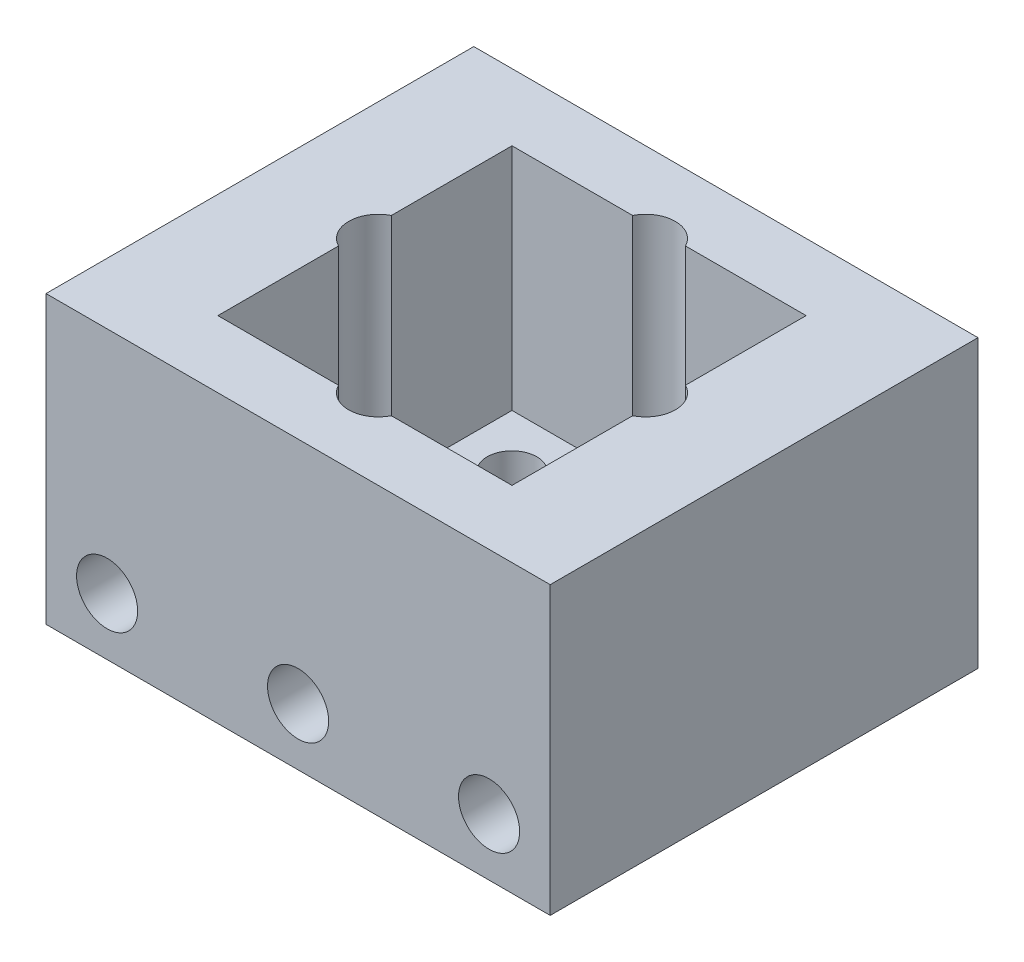
SolidWorks part; units mm, degrees
note: The reader was unsure of these and kept them because the rebuilt part matched: shared geometry of "草图1<4>", "草图1<5>".
ref_plane "前视基准面" through (0, 0, 0) normal (0, 0, 1) x (1, 0, 0)
ref_plane "上视基准面" through (0, 0, 0) normal (0, 1, 0) x (1, 0, 0)
ref_plane "右视基准面" through (0, 0, 0) normal (1, 0, 0) x (0, 0, -1)
sketch "草图1" plane through (0, 0, 0) normal (0, 1, 0) x (1, 0, 0)
  line L0 (0, 0) -> (0, 7.7) construction
  line L1 (0, 0) -> (0, -7.7) construction
  line L2 (0, 0) -> (7.7, 0) construction
  line L3 (0, 0) -> (-7.7, 0) construction
  line L4 (0, 7.7) -> (7.7, 7.7)
  line L5 (7.7, 7.7) -> (7.7, 0)
  line L6 (7.7, -7.7) -> (0, -7.7)
  line L7 (-7.7, -7.7) -> (-7.7, 0)
  line L8 (-7.7, 7.7) -> (0, 7.7)
  line L9 (-7.7, 0) -> (-7.7, 7.7)
  line L10 (-7.7, -7.7) -> (0, -7.7)
  line L11 (7.7, -7.7) -> (7.7, 0)
  line L12 (-7.7, -7.7) -> (-7.7, -11.2)
  line L13 (7.7, -7.7) -> (7.7, -11.2)
  line L14 (-7.7, 11.2) -> (-7.7, 7.7)
  line L15 (7.7, 7.7) -> (7.7, 11.2)
  line L19 (-7.7, 11.2) -> (7.7, 11.2)
  line L22 (7.7, -11.2) -> (-7.7, -11.2)
  line L28 (-7.7, -7.7) -> (-4.7, -7.7)
  line L30 (7.7, 11.2) -> (13.2, 11.2)
  line L32 (13.2, 11.2) -> (13.2, -11.2)
  line L33 (7.7, -11.2) -> (13.2, -11.2)
  line L34 (-7.7, -11.2) -> (-13.2, -11.2)
  line L35 (-13.2, -11.2) -> (-13.2, 11.2)
  line L36 (-13.2, 11.2) -> (-7.7, 11.2)
extrude "凸台-拉伸2" add sketch "草图1" along normal blind 3
extrude "凸台-拉伸3" add sketch "草图1<4>" along normal blind 10 separate body
sketch "草图1<4>" plane through (0, 0, 0) normal (0, 1, 0) x (1, 0, 0) same geometry as "草图1"
extrude "凸台-拉伸4" add sketch "草图1<5>" along normal blind 15
sketch "草图1<5>" plane through (0, 0, 0) normal (0, 1, 0) x (1, 0, 0) same geometry as "草图1"
sketch "草图3" plane through (0, 0, -19.6) normal (0, 0, -1) x (-1, 0, 0)
  line L3 (0, 3) -> (10, 3)
  line L6 (0, 0) -> (0, 3) construction
  line L9 (17.5, 0) -> (-17.5, 0) construction
  line L10 (0, 3) -> (0, 3)
  line L11 (0, 3) -> (-10, 3)
  circle A0 centre (0, 3) radius 1.6
  circle A1 centre (-10, 3) radius 1.6
  circle A2 centre (10, 3) radius 1.6
  point P1 (0, 0)
  point P2 (0, 0)
  point P3 (0, 0)
  point P4 (0, 0)
  point P21 (0, 0)
extrude "切除-拉伸2" cut sketch "草图3" against normal through all
sketch "草图8" plane through (-13.2, 0, 0) normal (-1, 0, 0) x (0, 0, 1)
  line L0 (10, 10) -> (10, 3)
  line L1 (0, 3) -> (10, 3)
  line L2 (10, 10) -> (10, 13)
  line L3 (-10, 3) -> (0, 3)
  line L10 (-10, 3) -> (-10, 13)
  line L11 (-10, 13) -> (10, 13)
sketch "草图9" plane through (0, 0, 0) normal (0, -1, 0) x (1, 0, 0)
  line L0 (0, 0) -> (-7, 0) construction
  line L1 (0, 0) -> (7, 0) construction
  line L2 (0, 0) -> (0, -7) construction
  line L3 (0, 0) -> (0, 7) construction
  line L4 (0, 7) -> (-7, 7) construction
  line L5 (-7, 7) -> (-7, 0) construction
  line L6 (-7, 0) -> (-7, -7) construction
  line L7 (-7, -7) -> (0, -7) construction
  line L8 (7, -7) -> (7, 0) construction
  line L9 (7, -7) -> (0.5896, -7) construction
  line L10 (7, 0) -> (7, 7) construction
  line L11 (7, 7) -> (0, 7) construction
  line L12 (-7, 7) -> (7, -7) construction
  line L13 (-7, -7) -> (7, 7) construction
  line L14 (0, 0) -> (-4.9497, 4.9497) construction
  line L15 (0, 0) -> (-4.9497, -4.9497) construction
  line L16 (0, 0) -> (4.9497, -4.9497) construction
  line L17 (0, 0) -> (4.9497, 4.9497) construction
  circle A0 centre (-4.9497, -4.9497) radius 1.3
  circle A1 centre (4.9497, -4.9497) radius 1.3
  circle A2 centre (4.9497, 4.9497) radius 1.3
  circle A3 centre (-4.9497, 4.9497) radius 1.3
  circle A4 centre (0, 0) radius 3
  circle A5 centre (7, 0) radius 1.55
  circle A6 centre (0, 7) radius 1.55
  circle A7 centre (0, -7) radius 1.55
  circle A8 centre (-7, 0) radius 1.55
extrude "切除-拉伸6" cut sketch "草图9" against normal through all
sketch "草图10" plane through (0, 0, -11.2) normal (0, 0, -1) x (-1, 0, 0)
  circle A0 centre (10, 3) radius 2.9
  circle A1 centre (0, 3) radius 2.9
  circle A2 centre (-10, 3) radius 2.9
extrude "切除-拉伸7" cut sketch "草图10" against normal blind 2
